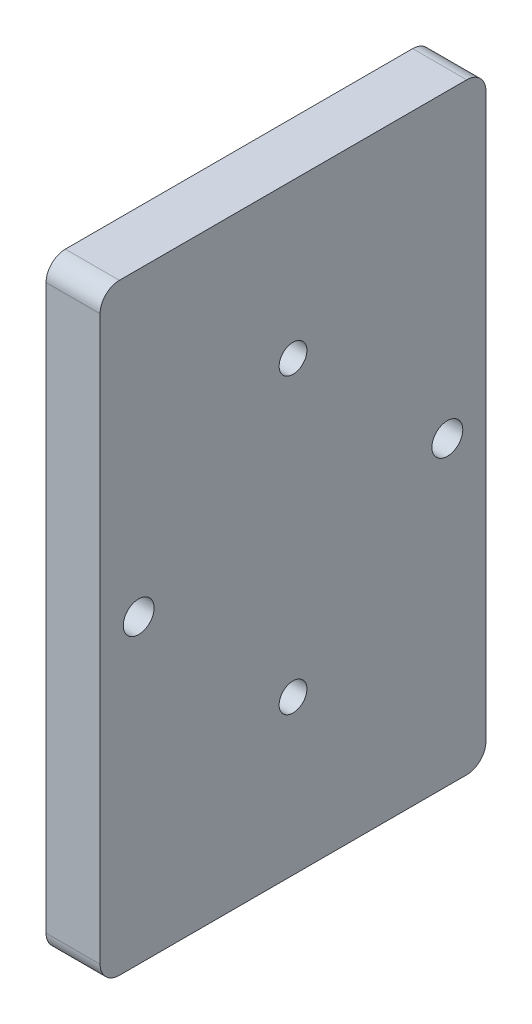
SolidWorks part; units mm, degrees
material "1060 Alloy"
ref_plane "Front Plane" through (0, 0, 0) normal (0, 0, 1) x (1, 0, 0)
ref_plane "Top Plane" through (0, 0, 0) normal (0, 1, 0) x (1, 0, 0)
ref_plane "Right Plane" through (0, 0, 0) normal (1, 0, 0) x (0, 0, -1)
sketch "Sketch1" plane through (0, 0, 0) normal (1, 0, 0) x (0, 0, -1)
  line L0 (0, 0) -> (0, 156)
  line L1 (0, 156) -> (100, 156)
  line L2 (100, 156) -> (100, 0)
  line L3 (100, 0) -> (0, 0)
  line L4 (0, 0) -> (100, 156) construction
  line L5 (100, 0) -> (0, 156) construction
  line L6 (50, 156) -> (50, 0) construction
  line L7 (100, 78) -> (0, 78) construction
  circle A0 centre (50, 40) radius 3.6
  circle A1 centre (50, 116) radius 3.6
  circle A2 centre (10, 78) radius 4
  circle A3 centre (90, 78) radius 4
  circle A4 centre (50, 116) radius 7
  circle A5 centre (50, 40) radius 7
  dimension "D3" = 7.2
  dimension "D6" = 10
  dimension "D8" = 8
  dimension "D9" = 14
  dimension "D1" = 100
  dimension "D2" = 156
  dimension "D4" = 76
  dimension "D5" = 40
  dimension "D7" = 10
extrude "Boss-Extrude1" add sketch "Sketch1" along normal blind 14 contours L3 L2 L1 L0 A5 A4 A3 A2 | A5 A0 | A4 A1 region at (0, 78, -50) region at (0, 116, -43.198) region at (0, 40, -43.198)
fillet "Fillet1" radius 5 4 edges at (7, 156, -100) (7, 156, 0) (7, 0, 0) (7, 0, -100)
extrude "Cut-Extrude1" cut sketch "Sketch1<3>" along normal blind 8 contours A4 A1 | A5 A0 region at (0, 116, -43.198) region at (0, 40, -43.198)
sketch "Sketch1<3>" plane through (0, 0, 0) normal (1, 0, 0) x (0, 0, -1) same geometry as "Sketch1"
